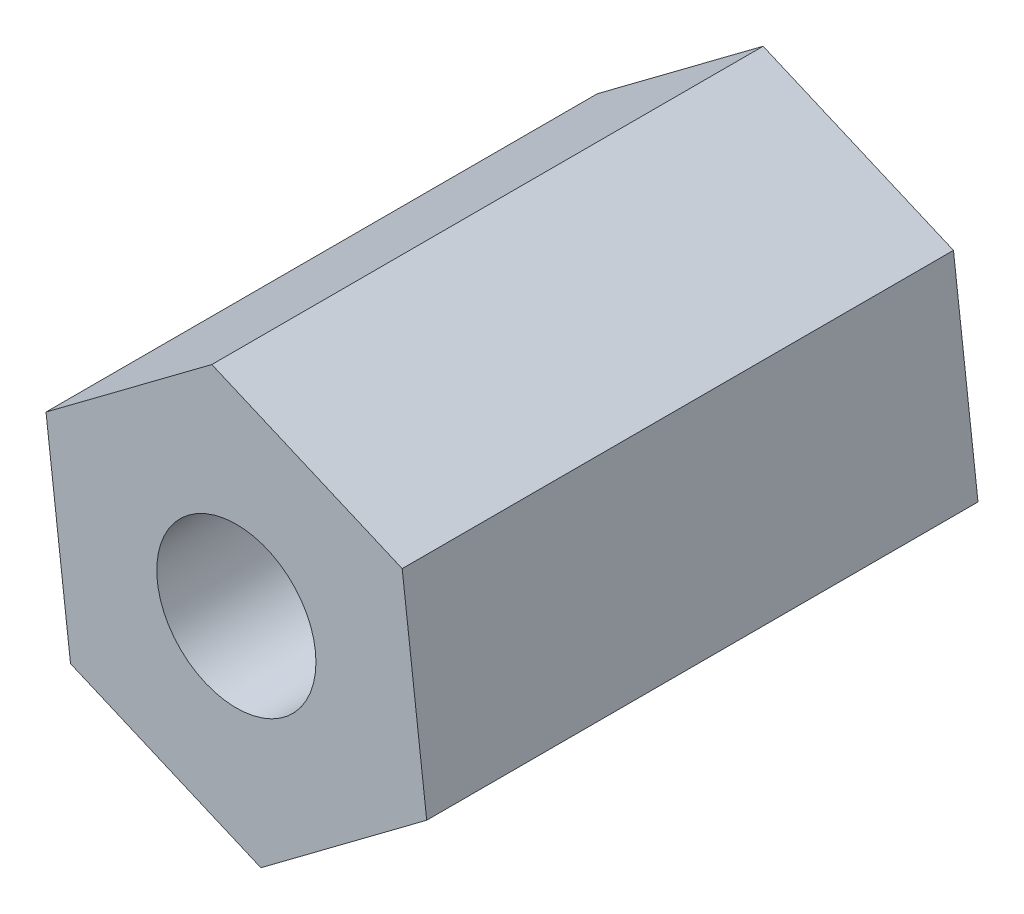
SolidWorks part; units mm, degrees
ref_plane "Front Plane" through (0, 0, 0) normal (0, 0, 1) x (1, 0, 0)
ref_plane "Top Plane" through (0, 0, 0) normal (0, 1, 0) x (1, 0, 0)
ref_plane "Right Plane" through (0, 0, 0) normal (1, 0, 0) x (0, 0, -1)
sketch "Sketch7" plane through (0, 0, 0) normal (0, 0, 1) x (1, 0, 0)
  line L1 (-76.4398, 4.7385) -> (-76.8624, 8.2821)
  line L2 (-76.8624, 8.2821) -> (-80.1426, 9.6879)
  line L3 (-80.1426, 9.6879) -> (-83.0001, 7.5501)
  line L4 (-83.0001, 7.5501) -> (-82.5774, 4.0065)
  line L5 (-82.5774, 4.0065) -> (-79.2973, 2.6007)
  line L6 (-79.2973, 2.6007) -> (-76.4398, 4.7385)
  circle A0 centre (-79.7199, 6.1443) radius 3.0906 construction
  circle A1 centre (-79.7199, 6.1443) radius 1.3716
  dimension "D2" = 2.7432
  dimension "D1" = 7.1374
extrude "Boss-Extrude4" add sketch "Sketch7" along normal mid plane 9.4996 separate body
ref_axis "Axis2" through (-79.7199, 6.1443, 11.6545) along (0, 0, -1)
equation "\"D2@Sketch7\" = \"screwDiameter\""
equation "\"screwDiameter\"=\"0.108\""
equation "\"standoffHeight\"=\"0.374\""
equation "\"D1@Boss-Extrude4\" = \"standoffHeight\""
